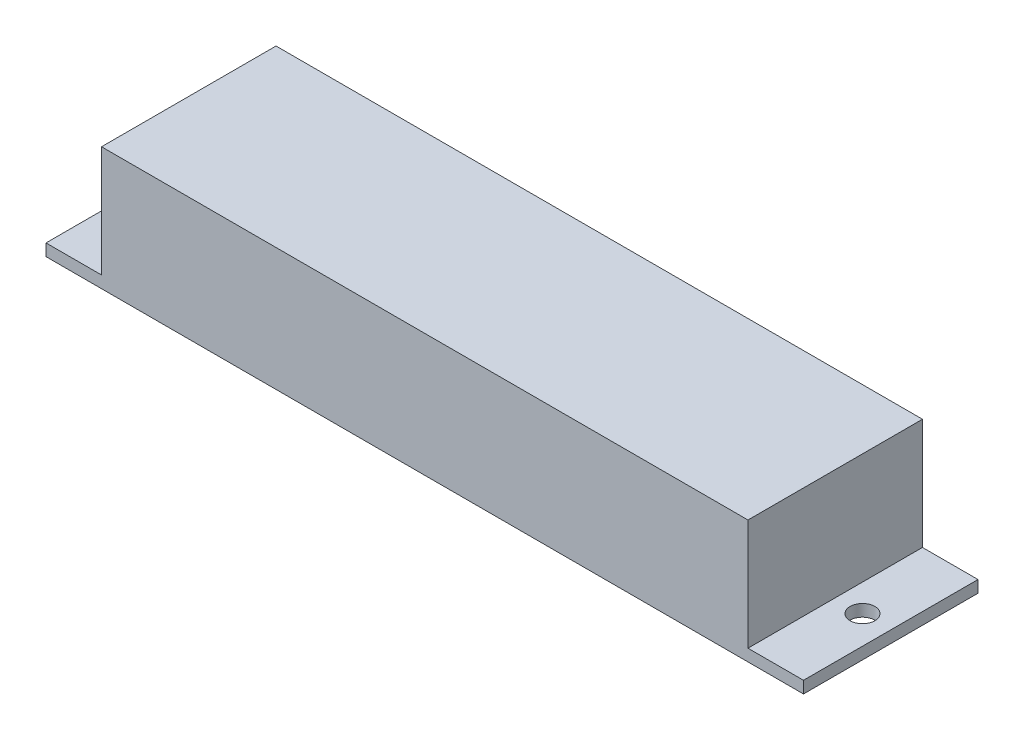
SolidWorks part; units mm, degrees
ref_plane "Front Plane" through (0, 0, 0) normal (0, 0, 1) x (1, 0, 0)
ref_plane "Top Plane" through (0, 0, 0) normal (0, 1, 0) x (1, 0, 0)
ref_plane "Right Plane" through (0, 0, 0) normal (1, 0, 0) x (0, 0, -1)
sketch "Sketch1" plane through (0, 0, 0) normal (0, 1, 0) x (1, 0, 0)
  line L0 (22.8051, 11.176) -> (22.8051, -11.176)
  line L1 (-25.7089, 11.176) -> (71.3191, 11.176)
  line L2 (-25.7089, 11.176) -> (-25.7089, -11.176)
  line L3 (-25.7089, -11.176) -> (71.3191, -11.176)
  line L4 (71.3191, 11.176) -> (71.3191, -11.176)
  line L5 (-18.5969, 11.176) -> (-18.5969, -11.176)
  line L6 (64.2071, 11.176) -> (64.2071, -11.176)
  circle A0 centre (-22.0894, 0) radius 1.5875
  circle A1 centre (67.6996, 0) radius 1.5875
  point P7 (-25.7089, 0)
  dimension "D3" = 3.6195
  dimension "D1" = 22.352
  dimension "D2" = 97.028
  dimension "D4" = 7.112
extrude "Boss-Extrude1" add sketch "Sketch1" along normal blind 1.524 contours A1 | A0 | L2 L3 L4 L1
extrude "Boss-Extrude2" add sketch "Sketch1<3>" along normal blind 15.748 contours L1 L5 L3 L0 | L6 L1 L0 L3 region at (43.5061, 0, 0) region at (2.1041, 0, 0)
sketch "Sketch1<3>" plane through (0, 0, 0) normal (0, 1, 0) x (1, 0, 0) same geometry as "Sketch1"
